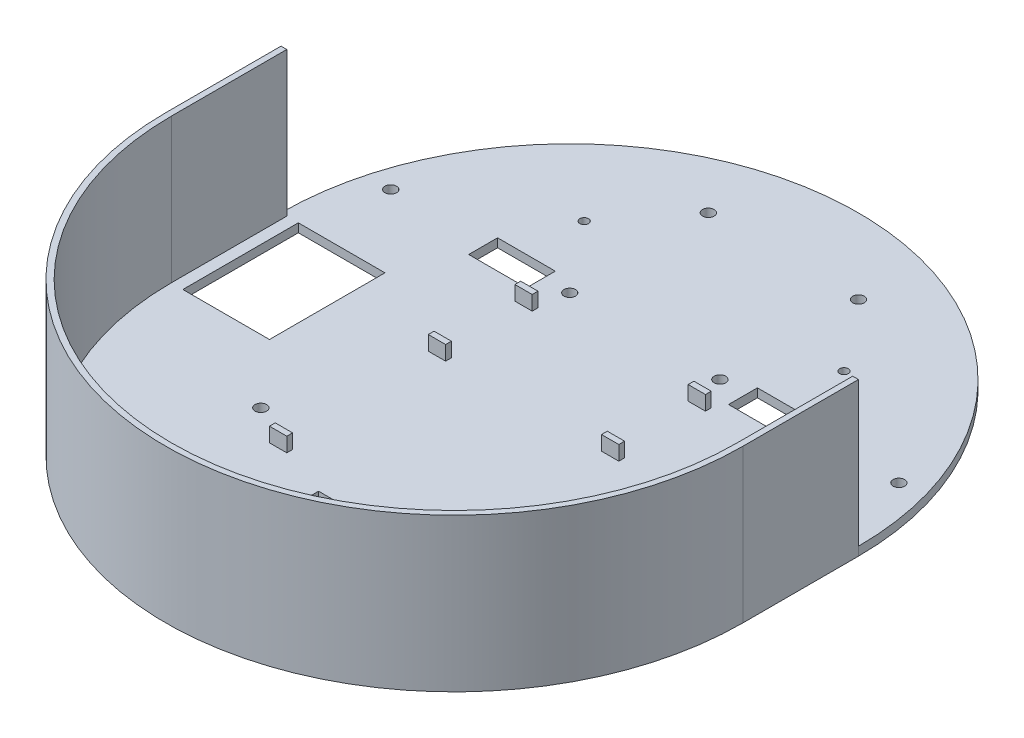
SolidWorks part; units mm, degrees
ref_plane "前视基准面" through (0, 0, 0) normal (0, 0, 1) x (1, 0, 0)
ref_plane "上视基准面" through (0, 0, 0) normal (0, 1, 0) x (1, 0, 0)
ref_plane "右视基准面" through (0, 0, 0) normal (1, 0, 0) x (0, 0, -1)
sketch "草图1" plane through (0, 0, 0) normal (0, 1, 0) x (1, 0, 0)
  line L1 (100, 0) -> (-100, 0)
  line L2 (100, 0) -> (100, 40)
  line L3 (100, 40) -> (-100, 40)
  line L4 (-100, 0) -> (-100, 40)
  circle A0 centre (0, 0) radius 100
  circle A1 centre (0, 40) radius 100
  dimension "D1" = 200
  dimension "D2" = 40
extrude "基础板" add sketch "草图1" along normal blind 3 contours L4 L3 L2 L1 | A0 | A1
sketch "草图5" plane through (0, 3, 0) normal (0, 1, 0) x (1, 0, 0)
  line L2 (-98, 40) -> (-100, 40)
  line L3 (98, 40) -> (100, 40)
  line L4 (98, 0) -> (98, 40)
  line L5 (-98, 40) -> (-98, 0)
  line L6 (98, 0) -> (98, 40)
  line L7 (-98, 40) -> (-98, 0)
  arc A2 (100, 40) -> (-100, 40) centre (0, 40) ccw construction
  arc A4 (-98, 0) -> (98, 0) centre (0, 0) ccw
  arc A5 (98, 40) -> (-98, 40) centre (0, 40) ccw
  arc A6 (-98, 0) -> (98, 0) centre (0, 0) ccw
  line M5 (-100, 40) -> (-100, 0)
  arc M6 (-100, 0) -> (100, 0) centre (0, 0) ccw
  line M7 (100, 0) -> (100, 40)
  arc M8 (100, 40) -> (-100, 40) centre (0, 40) ccw
  dimension "D1" = 2
extrude "外壁" add sketch "草图5" along normal blind 50 contours L6 A6 L7 M8 M5 M6 M7 region at (-98.2441, 3, -20)
sketch "草图3" plane through (0, 3, 0) normal (0, 1, 0) x (1, 0, 0)
  line L0 (0, 13.3527) -> (0, 34.0531)
  line L1 (-94, 40) -> (-64, 40)
  line L2 (-94, 40) -> (-94, 0)
  line L3 (-94, 0) -> (-64, 0)
  line L4 (-64, 40) -> (-64, 0)
  line L5 (64, 40) -> (64, 0)
  line L6 (94, 0) -> (64, 0)
  line L7 (94, 40) -> (94, 0)
  line L8 (94, 40) -> (64, 40)
  line L9 (-100, 0) -> (-100, 40) construction
  line L10 (35, 70) -> (35, 60)
  line L11 (-10, -67) -> (10, -67)
  line L12 (-10, -67) -> (-10, -37)
  line L13 (-10, -37) -> (10, -37)
  line L14 (10, -67) -> (10, -37)
  line L15 (-10, -67) -> (10, -37) construction
  line L16 (-10, -37) -> (10, -67) construction
  line L17 (-55, 70) -> (-35, 70)
  line L18 (-55, 70) -> (-55, 60)
  line L19 (-55, 60) -> (-35, 60)
  line L20 (-35, 70) -> (-35, 60)
  line L21 (55, 60) -> (35, 60)
  line L22 (55, 70) -> (55, 60)
  line L23 (55, 70) -> (35, 70)
  point P13 (0, -52)
  dimension "D1" = 6
  dimension "D2" = 30
  dimension "D3" = 52
  dimension "D4" = 30
  dimension "D5" = 20
  dimension "D6" = 60
  dimension "D7" = 35
  dimension "D8" = 20
  dimension "D9" = 10
extrude "过孔" cut sketch "草图3" against normal blind 3 contours L4 L1 L2 L3 | L7 L8 L5 L6 | L11 L14 L13 L12 | L20 L17 L18 L19 | L22 L23 L10 L21 region at (-79, 3, -20) region at (79, 3, -20) region at (45, 3, -65) region at (0, 3, 52) region at (-45, 3, -65)
sketch "草图2" plane through (0, 3, 0) normal (0, 1, 0) x (1, 0, 0)
  line L0 (0, -7.8134) -> (0, -32.4764)
  circle A0 centre (-45, -22) radius 2
  circle A1 centre (-40, -82) radius 2
  circle A2 centre (-88, 66) radius 2
  circle A3 centre (-26, 66) radius 2
  circle A4 centre (-26, 114) radius 2
  circle A5 centre (40, -82) radius 2
  circle A6 centre (45, -22) radius 2
  circle A7 centre (26, 114) radius 2
  circle A8 centre (26, 66) radius 2
  circle A9 centre (88, 66) radius 2
  circle A10 centre (-45, 90) radius 1.5
  circle A11 centre (45, 90) radius 1.5
  point P15 (0, 0)
  point P26 (0, 0)
  dimension "D1" = 4
  dimension "D2" = 4
  dimension "D3" = 4
  dimension "D4" = 4
  dimension "D5" = 4
  dimension "D6" = 45
  dimension "D7" = 22
  dimension "D8" = 40
  dimension "D9" = 82
  dimension "D10" = 26
  dimension "D11" = 88
  dimension "D12" = 26
  dimension "D13" = 66
  dimension "D14" = 66
  dimension "D15" = 114
  dimension "D16" = 3
  dimension "D17" = 90
  dimension "D18" = 45
extrude "螺丝孔" cut sketch "草图2" against normal through all contours A2 | A3 | A4 | A7 | A8 | A9 | A0 | A6 | A1 | A5 | A10 | A11 region at (-45, 3, 22) region at (-40, 3, 82) region at (-88, 3, -66) region at (-26, 3, -66) region at (-26, 3, -114) region at (40, 3, 82) region at (45, 3, 22) region at (26, 3, -114) region at (26, 3, -66) region at (88, 3, -66) region at (-45, 3, -90) region at (45, 3, -90)
sketch "草图6" plane through (0, 3, 0) normal (0, 1, 0) x (1, 0, 0)
  line L0 (0, -21.4979) -> (0, -29.8491)
  line L1 (33, -61) -> (27, -59) construction
  line L2 (-33, -29) -> (-27, -29)
  line L3 (-33, -29) -> (-33, -31)
  line L4 (-33, -31) -> (-27, -31)
  line L5 (-27, -29) -> (-27, -31)
  line L6 (-33, -29) -> (-27, -31) construction
  line L7 (-33, -31) -> (-27, -29) construction
  line L8 (-33, -59) -> (-27, -59)
  line L9 (-33, -59) -> (-33, -61)
  line L10 (-33, -61) -> (-27, -61)
  line L11 (-27, -59) -> (-27, -61)
  line L12 (-33, -59) -> (-27, -61) construction
  line L13 (-33, -61) -> (-27, -59) construction
  line L14 (-33, 26) -> (-27, 26)
  line L15 (-33, 26) -> (-33, 24)
  line L16 (-33, 24) -> (-27, 24)
  line L17 (-27, 26) -> (-27, 24)
  line L18 (-33, 26) -> (-27, 24) construction
  line L19 (-33, 24) -> (-27, 26) construction
  line L20 (-33, 56) -> (-27, 56)
  line L21 (-33, 56) -> (-33, 54)
  line L22 (-33, 54) -> (-27, 54)
  line L23 (-27, 56) -> (-27, 54)
  line L24 (-33, 56) -> (-27, 54) construction
  line L25 (-33, 54) -> (-27, 56) construction
  line L26 (33, -59) -> (27, -61) construction
  line L27 (27, -59) -> (27, -61)
  line L28 (33, -61) -> (27, -61)
  line L29 (33, -59) -> (33, -61)
  line L30 (33, -59) -> (27, -59)
  line L31 (33, -31) -> (27, -29) construction
  line L32 (33, -29) -> (27, -31) construction
  line L33 (27, -29) -> (27, -31)
  line L34 (33, -31) -> (27, -31)
  line L35 (33, -29) -> (33, -31)
  line L36 (33, -29) -> (27, -29)
  line L37 (33, 54) -> (27, 56) construction
  line L38 (33, 56) -> (27, 54) construction
  line L39 (27, 56) -> (27, 54)
  line L40 (33, 54) -> (27, 54)
  line L41 (33, 56) -> (33, 54)
  line L42 (33, 56) -> (27, 56)
  line L43 (33, 24) -> (27, 26) construction
  line L44 (33, 26) -> (27, 24) construction
  line L45 (27, 26) -> (27, 24)
  line L46 (33, 24) -> (27, 24)
  line L47 (33, 26) -> (33, 24)
  line L48 (33, 26) -> (27, 26)
  point P3 (-30, -30)
  point P8 (-30, -60)
  point P13 (-30, 25)
  point P18 (-30, 55)
  point P25 (0, 0)
  point P26 (23.3843, -21.9722)
  point P27 (-6.5781, -31.2194)
  point P30 (30, -60)
  point P35 (30, -30)
  point P40 (30, 55)
  point P45 (30, 25)
  dimension "D1" = 30
  dimension "D2" = 30
  dimension "D3" = 6
  dimension "D4" = 2
  dimension "D5" = 60
  dimension "D6" = 30
  dimension "D7" = 6
  dimension "D8" = 2
  dimension "D9" = 6
  dimension "D10" = 2
  dimension "D11" = 6
  dimension "D12" = 2
  dimension "D13" = 30
  dimension "D14" = 30
  dimension "D15" = 25
  dimension "D16" = 55
extrude "固定卡槽" add sketch "草图6" along normal blind 5 contours L20 L23 L22 L21 | L14 L17 L16 L15 | L42 L39 L40 L41 | L48 L45 L46 L47 | L2 L5 L4 L3 | L8 L11 L10 L9 | L36 L33 L34 L35 | L30 L27 L28 L29
